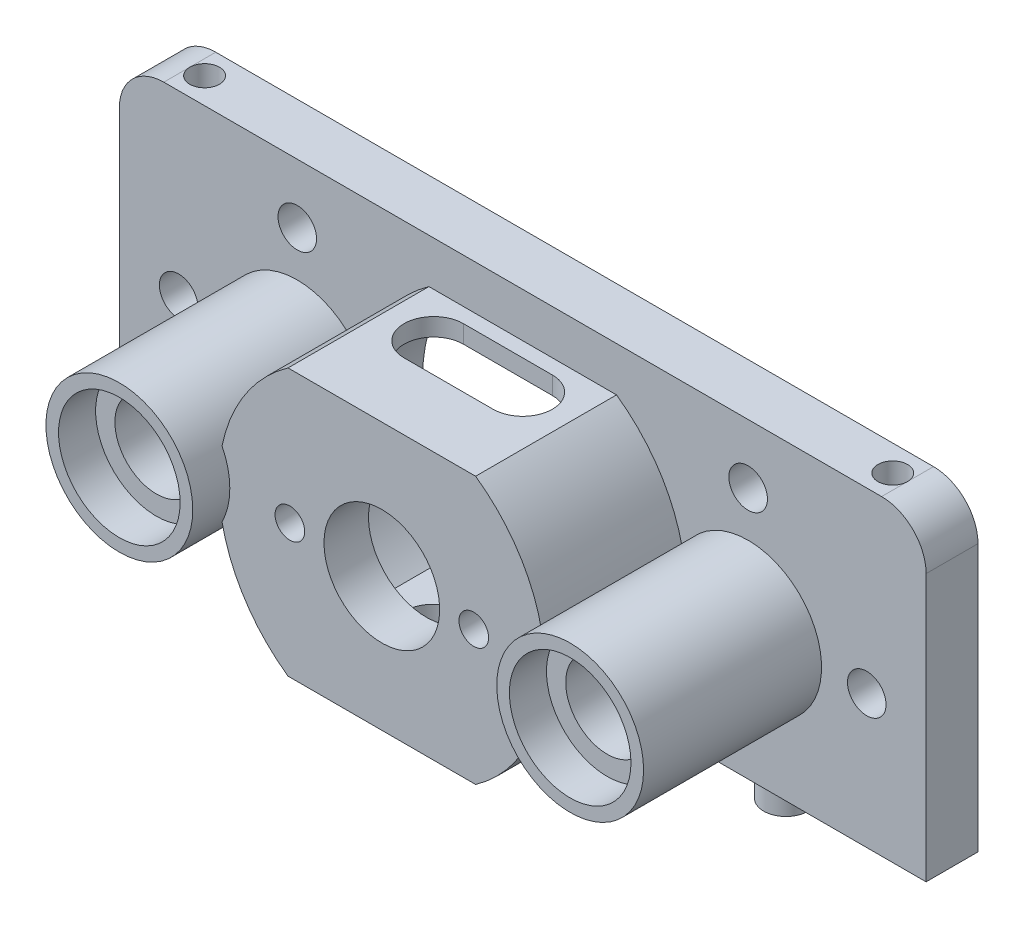
SolidWorks part; units mm, degrees
ref_plane "前视基准面" through (0, 0, 0) normal (0, 0, 1) x (1, 0, 0)
ref_plane "上视基准面" through (0, 0, 0) normal (0, 1, 0) x (1, 0, 0)
ref_plane "右视基准面" through (0, 0, 0) normal (1, 0, 0) x (0, 0, -1)
other "Configuration Table"
sketch "草图2" plane through (0, 0, 0) normal (0, 0, 1) x (1, 0, 0)
  line L0 (0, 0) -> (11.5094, 0) construction
  line L1 (0, 0) -> (0, 7.1412) construction
  line L2 (15.2, 0) -> (-15.2, 0) construction
  line L3 (15.2, -20) -> (-15.2, -20)
  line L4 (15.2, 20) -> (-15.2, 20)
  circle A0 centre (0, 0) radius 3.9
  circle A1 centre (-15.2, 0) radius 2.8
  circle A2 centre (-15.2, 0) radius 4.1
  arc A3 (15.2, -20) -> (15.2, 20) centre (15.2, 0) ccw
  arc A4 (-15.2, 20) -> (-15.2, -20) centre (-15.2, 0) ccw
  circle A5 centre (15.2, 0) radius 2.8
  circle A6 centre (15.2, 0) radius 4.1
  circle A7 centre (-6.2, 0) radius 1
  circle A9 centre (6.2, 0) radius 1
  circle A11 centre (-15.2, 8) radius 1.3
  circle A12 centre (-23.2, 0) radius 1.3
  circle A15 centre (23.2, 0) radius 1.3
  circle A16 centre (15.2, 8) radius 1.3
  point P11 (0, 0)
  dimension "D1" = 7.8
  dimension "D2" = 5.6
  dimension "D4" = 8.2
  dimension "D5" = 20
  dimension "D6" = 2
  dimension "D10" = 2.6
  dimension "D12" = 2.6
  dimension "D3" = 15.2
  dimension "D7" = 6.2
  dimension "D11" = 8
  dimension "D13" = 8
extrude "凸台-拉伸1" add sketch "草图2" along normal blind 3.5 contours L4 A4 L3 A3 A15 A6 A2 A0 A7 A9 A11 A12 A16 region at (0, -19.1903, 0)
extrude "凸台-拉伸2" add sketch "草图2<4>" along normal blind 1 contours A2 A1 | A6 A5 region at (-19.184, 0, 0) region at (11.216, 0, 0)
sketch "草图2<4>" plane through (0, 0, 0) normal (0, 0, 1) x (1, 0, 0) same geometry as "草图2"
sketch "草图3" plane through (0, 0, 3.5) normal (0, 0, 1) x (1, 0, 0)
  line L3 (15.2, -20) -> (-15.2, -20) construction
  line L4 (15.2, 20) -> (-15.2, 20) construction
  line L5 (15.2, -20) -> (-15.2, -20)
  line L6 (15.2, 20) -> (-15.2, 20)
  line L7 (-27.2, 12) -> (27.2, 12)
  line L8 (-27.2, 12) -> (-27.2, -9)
  line L9 (-27.2, -9) -> (27.2, -9)
  line L10 (27.2, 12) -> (27.2, -9)
  arc A2 (15.2, -20) -> (15.2, 20) centre (15.2, 0) ccw construction
  arc A3 (-15.2, 20) -> (-15.2, -20) centre (-15.2, 0) ccw construction
  arc A4 (15.2, -20) -> (15.2, 20) centre (15.2, 0) ccw
  arc A5 (-15.2, 20) -> (-15.2, -20) centre (-15.2, 0) ccw
  line M9 (15.2, 20) -> (-15.2, 20)
  arc M10 (-15.2, 20) -> (-15.2, -20) centre (-15.2, 0) ccw
  line M11 (-15.2, -20) -> (15.2, -20)
  arc M12 (15.2, -20) -> (15.2, 20) centre (15.2, 0) ccw
  dimension "D1" = 9
  dimension "D2" = 12
  dimension "D3" = 12
  dimension "D4" = 12
extrude "切除-拉伸1" cut sketch "草图3" against normal through all both and the other way through all contours M12 M9 M10 | M10 M11 M12 region at (0, -19.1903, 3.5)
fillet "圆角1" radius 3 2 edges at (-27.2, 12, 1.75) (27.2, 12, 1.75)
sketch "草图4" plane through (0, -9, 0) normal (0, -1, 0) x (1, 0, 0)
  line L0 (0, 0) -> (0, 12.3535) construction
  line L1 (-27.2, 3.5) -> (27.2, 3.5) construction
  line L2 (-27.2, 0) -> (-27.2, 3.5) construction
  line L3 (-12.4, 1) -> (-18, 1) construction
  line L4 (-12.4, 1) -> (-18, 1) construction
  circle A0 centre (-16, 1.75) radius 1.5
  circle A2 centre (-24, 1.75) radius 1
  circle A4 centre (16, 1.75) radius 1.5
  circle A5 centre (24, 1.75) radius 1
  point P26 (-15.2, 1)
  dimension "D1" = 3
  dimension "D6" = 2
  dimension "D8" = 27.2
  dimension "D2" = 1.75
  dimension "D3" = 16
  dimension "D7" = 24
  dimension "D9" = 0.8
extrude "切除-拉伸2" cut sketch "草图4" against normal blind 7 and the other way through all contours A2 | A5
extrude "凸台-拉伸3" add sketch "草图4<4>" along normal blind 1.6 contours A0 | A4 region at (-16, -9, 1.75) region at (16, -9, 1.75)
sketch "草图4<4>" plane through (0, -9, 0) normal (0, -1, 0) x (1, 0, 0) same geometry as "草图4"
sketch "草图5" plane through (0, 0, 0) normal (0, 0, -1) x (-1, 0, 0)
  line L0 (-6.3246, 9) -> (6.3246, 9)
  line L1 (-6.3246, -9) -> (6.3246, -9)
  line L5 (27.2, -9) -> (27.2, 9)
  line L6 (24.2, 12) -> (-24.2, 12)
  line L7 (-27.2, 9) -> (-27.2, -9)
  line L8 (-27.2, -9) -> (27.2, -9)
  line L9 (27.2, -9) -> (27.2, 9)
  line L10 (24.2, 12) -> (-24.2, 12)
  line L11 (-27.2, 9) -> (-27.2, -9)
  line L12 (-27.2, -9) -> (27.2, -9)
  circle A1 centre (0, 0) radius 11
  circle A2 centre (-6.2, 0) radius 1 construction
  circle A4 centre (6.2, 0) radius 1 construction
  circle A6 centre (0, 0) radius 3.9 construction
  circle A7 centre (-6.2, 0) radius 1
  circle A9 centre (6.2, 0) radius 1
  circle A11 centre (0, 0) radius 3.9
  arc A14 (27.2, 9) -> (24.2, 12) centre (24.2, 9) ccw
  arc A15 (-24.2, 12) -> (-27.2, 9) centre (-24.2, 9) ccw
  arc A16 (27.2, 9) -> (24.2, 12) centre (24.2, 9) ccw
  arc A17 (-24.2, 12) -> (-27.2, 9) centre (-24.2, 9) ccw
  circle M13 centre (-6.2, 0) radius 1
  circle M15 centre (6.2, 0) radius 1
  circle M16 centre (0, 0) radius 3.9
  dimension "D1" = 22
  dimension "D3" = 18
  dimension "D4" = 9
  dimension "D2" = 0
extrude "凸台-拉伸4" add sketch "草图5" against normal blind 13 contours L12 A1 M13 M15 M16 region at (0, 8.7157, 0)
sketch "草图6" plane through (0, 0, 0) normal (0, 0, -1) x (-1, 0, 0)
  line L0 (-6.65, 7.8) -> (6.65, 7.8)
  line L1 (6.65, -7.8) -> (-6.65, -7.8)
  circle A0 centre (0, 0) radius 10.25
  circle M17 centre (0, 0) radius 3.9
  circle M18 centre (6.2, 0) radius 1
  circle M20 centre (-6.2, 0) radius 1
  dimension "D1" = 20.5
  dimension "D3" = 15.6
extrude "切除-拉伸3" cut sketch "草图6" against normal offset from surface (10 mm away) 3 contours L0 A0 L1 M17 M20 M18 region at (0, 7.5424, 0) up to face at (-3.9, 0, 13)
sketch "草图7" plane through (0, 9, 0) normal (0, 1, 0) x (1, 0, 0)
  line L0 (-3, -6.5) -> (3, -6.5) construction
  line L1 (-3, -4.5) -> (3, -4.5)
  line L2 (-3, -8.5) -> (3, -8.5)
  line L3 (-24.2, -3.5) -> (24.2, -3.5) construction
  arc A0 (-3, -4.5) -> (-3, -8.5) centre (-3, -6.5) ccw
  arc A1 (3, -8.5) -> (3, -4.5) centre (3, -6.5) ccw
  point P2 (0, -6.5)
  dimension "D2" = 2
  dimension "D1" = 6
  dimension "D3" = 3
extrude "切除-拉伸4" cut sketch "草图7" against normal through all both and the other way through all
extrude "凸台-拉伸5" add sketch "草图2<5>" along normal blind 13 contours A2 A1 | A6 A5 region at (-19.184, 0, 0) region at (11.216, 0, 0)
sketch "草图2<5>" plane through (0, 0, 0) normal (0, 0, 1) x (1, 0, 0) same geometry as "草图2"
sketch "草图8" plane through (0, 0, 3.5) normal (0, 0, 1) x (1, 0, 0)
  line L0 (0, 0) -> (0, -7.8) construction
  arc A0 (-6.65, 7.8) -> (-6.65, -7.8) centre (0, 0) ccw construction
  arc A1 (-6.65, 7.8) -> (-6.65, -7.8) centre (0, 0) ccw
  circle A2 centre (-15.2, 0) radius 4.95
  circle A3 centre (15.2, 0) radius 4.95
  circle M3 centre (-15.2, 0) radius 4.1
  circle M4 centre (15.2, 0) radius 4.1
  arc M14 (-6.3246, -9) -> (-6.3246, 9) centre (0, 0) cw
  arc M16 (6.3246, 9) -> (6.3246, -9) centre (0, 0) cw
extrude "凸台-拉伸6" add sketch "草图8" along normal blind 12 contours A2 M14 M3 | A3 M16 M4 region at (-11.0136, 0, 3.5) region at (16.3077, -4.6845, 3.5)
extrude "凸台-拉伸7" add sketch "草图8<4>" along normal up to surface (12 mm away) from surface contours A2 M14 | A3 M16 region at (-10.6536, 0, 3.5) region at (10.6536, 0, 3.5) up to face at (15.575, 0, 15.5) starting at face at (-3.9, 0, 13)
sketch "草图8<4>" plane through (0, 0, 3.5) normal (0, 0, 1) x (1, 0, 0) same geometry as "草图8"
extrude "切除-拉伸10" cut sketch "草图2<6>" along normal blind 2.5 contours A2 A1 | A6 A5 region at (-19.184, 0, 0) region at (11.216, 0, 0)
sketch "草图2<6>" plane through (0, 0, 0) normal (0, 0, 1) x (1, 0, 0) same geometry as "草图2"
sketch "草图9" plane through (0, 12, 0) normal (0, 1, 0) x (1, 0, 0)
  line L0 (-24.2, 0) -> (24.2, 0) construction
  line L1 (24.2, -3.5) -> (24.2, 0) construction
  line L4 (-24.2, 0) -> (-24.2, -3.5) construction
  circle A0 centre (-23.2, -1.75) radius 1
  circle A1 centre (23.2, -1.75) radius 1
  dimension "D1" = 2
  dimension "D3" = 2
  dimension "D4" = 1.75
  dimension "D2" = 1.75
extrude "切除-拉伸11" cut sketch "草图9" against normal blind 6
